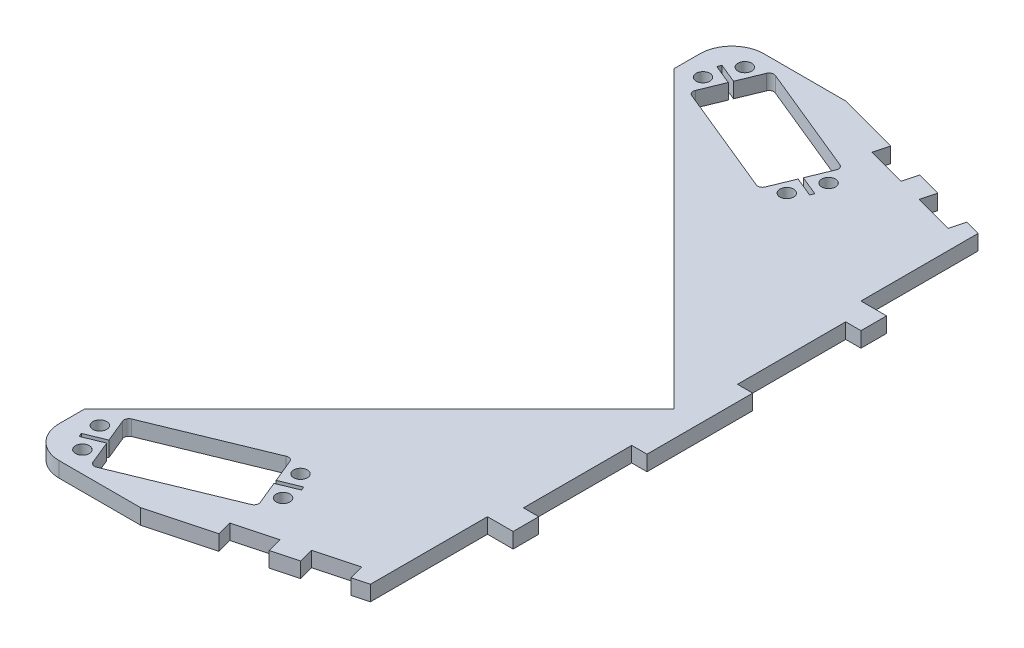
SolidWorks part; units mm, degrees
ref_plane "Front" through (0, 0, 0) normal (0, 0, 1) x (1, 0, 0)
ref_plane "Top" through (0, 0, 0) normal (0, 1, 0) x (1, 0, 0)
ref_plane "Right" through (0, 0, 0) normal (1, 0, 0) x (0, 0, -1)
ref_axis "side-side" through (80.9, 0, 0) along (-1, 0, 0)
ref_axis "up-down" through (0, 50, 0) along (0, -1, 0)
ref_axis "front-back" through (0, 0, -80.9) along (0, 0, 1)
sketch "Sketch1" plane through (0, 0, 0) normal (0, 1, 0) x (1, 0, 0)
  line L0 (-82.7905, 89.3902) -> (-79.7972, 96.6741)
  line L1 (0, 0) -> (-92, 92)
  line L2 (-92, 92) -> (-92, 110)
  line L3 (-79.322, 97.8303) -> (-76.3287, 105.1142)
  line L4 (-79.322, 97.8303) -> (-76.3287, 105.1142)
  line L5 (-92, 110) -> (-56.6019, 110)
  line L6 (8, 58.293) -> (8, -58.293)
  line L7 (0, 0) -> (58.8362, 0) construction
  line L8 (-92, -110) -> (-56.6019, -110)
  line L9 (-92, -110) -> (-92, -92)
  line L10 (0, 0) -> (-92, -92)
  line L11 (-82.7905, 89.3902) -> (-79.7972, 96.6741)
  line L12 (-42.3244, 82.6259) -> (-42.7995, 81.4697)
  line L13 (-42.7995, 81.4697) -> (-36.6949, 78.961)
  line L14 (-36.6949, 78.961) -> (-36.2198, 80.1172)
  line L15 (-36.2198, 80.1172) -> (-42.3244, 82.6259)
  line L16 (-56.6019, 110) -> (0, 94.8336)
  line L17 (-42.7995, 81.4697) -> (-36.6949, 78.961)
  line L18 (-36.6949, 78.961) -> (-36.2198, 80.1172)
  line L19 (-36.2198, 80.1172) -> (-42.3244, 82.6259)
  line L20 (-85.4267, 100.339) -> (-85.9018, 99.1828)
  line L21 (-85.9018, 99.1828) -> (-79.7972, 96.6741)
  line L22 (-79.7972, 96.6741) -> (-79.322, 97.8303)
  line L23 (-79.322, 97.8303) -> (-85.4267, 100.339)
  line L24 (-85.4267, 100.339) -> (-85.9018, 99.1828)
  line L25 (-85.9018, 99.1828) -> (-79.7972, 96.6741)
  line L26 (0, -94.8336) -> (-56.6019, -110)
  line L27 (-79.322, 97.8303) -> (-85.4267, 100.339)
  line L28 (-40.1483, 91.8674) -> (-74.3711, 105.9314)
  line L29 (-40.1483, 91.8674) -> (-74.3711, 105.9314)
  line L30 (-39.331, 89.9098) -> (-42.3244, 82.6259)
  line L31 (-42.7995, 81.4697) -> (-45.7929, 74.1858)
  line L32 (-42.7995, 81.4697) -> (-45.7929, 74.1858)
  line L33 (-39.331, 89.9098) -> (-42.3244, 82.6259)
  line L34 (-47.7504, 73.3685) -> (-81.9733, 87.4326)
  line L35 (-47.7504, 73.3685) -> (-81.9733, 87.4326)
  line L36 (-47.7504, -73.3685) -> (-81.9733, -87.4326)
  line L37 (-39.331, -89.9098) -> (-42.3244, -82.6259)
  line L38 (-42.7995, -81.4697) -> (-45.7929, -74.1858)
  line L39 (-40.1483, -91.8674) -> (-74.3711, -105.9314)
  line L40 (-79.322, -97.8303) -> (-85.4267, -100.339)
  line L41 (-85.9018, -99.1828) -> (-79.7972, -96.6741)
  line L42 (-85.4267, -100.339) -> (-85.9018, -99.1828)
  line L43 (-36.2198, -80.1172) -> (-42.3244, -82.6259)
  line L44 (-36.6949, -78.961) -> (-36.2198, -80.1172)
  line L45 (-42.7995, -81.4697) -> (-36.6949, -78.961)
  line L46 (-82.7905, -89.3902) -> (-79.7972, -96.6741)
  line L47 (-79.322, -97.8303) -> (-76.3287, -105.1142)
  line L50 (0, 94.8336) -> (0, 58.293)
  line L51 (0, 58.293) -> (8, 58.293)
  line L52 (0, -94.8336) -> (0, -58.293)
  line L53 (0, -58.293) -> (8, -58.293)
  arc A0 (-87.2208, 93.5353) -> (-86.1945, 96.0326) centre (-85.1599, 94.1479) ccw construction
  circle A1 centre (-85.1599, 94.1479) radius 2.15
  arc A2 (-83.4197, 102.7847) -> (-82.3934, 105.282) centre (-81.3588, 103.3973) ccw construction
  circle A3 centre (-81.3588, 103.3973) radius 2.15
  arc A4 (-34.9008, 85.7647) -> (-35.9271, 83.2673) centre (-36.9616, 85.1521) ccw construction
  circle A5 centre (-36.9616, 85.1521) radius 2.15
  arc A6 (-38.7018, 76.5153) -> (-39.7281, 74.0179) centre (-40.7627, 75.9026) ccw construction
  circle A7 centre (-40.7627, 75.9026) radius 2.15
  arc A8 (-74.3711, 105.9314) -> (-75.7356, 105.8164) centre (-74.9413, 104.544) ccw
  arc A9 (-75.7356, 105.8164) -> (-76.3287, 105.1142) centre (-74.9413, 104.544) ccw
  arc A10 (-75.7356, 105.8164) -> (-76.3287, 105.1142) centre (-74.9413, 104.544) ccw
  arc A11 (-74.3711, 105.9314) -> (-75.7356, 105.8164) centre (-74.9413, 104.544) ccw
  arc A12 (-82.7905, 89.3902) -> (-82.8626, 88.4738) centre (-81.4031, 88.82) ccw
  arc A13 (-82.8626, 88.4738) -> (-81.9733, 87.4326) centre (-81.4031, 88.82) ccw
  arc A14 (-82.8626, 88.4738) -> (-81.9733, 87.4326) centre (-81.4031, 88.82) ccw
  arc A15 (-82.7905, 89.3902) -> (-82.8626, 88.4738) centre (-81.4031, 88.82) ccw
  arc A16 (-39.331, 89.9098) -> (-39.2589, 90.8262) centre (-40.7184, 90.48) ccw
  arc A17 (-39.2589, 90.8262) -> (-40.1483, 91.8674) centre (-40.7184, 90.48) ccw
  arc A18 (-39.2589, 90.8262) -> (-40.1483, 91.8674) centre (-40.7184, 90.48) ccw
  arc A19 (-39.331, 89.9098) -> (-39.2589, 90.8262) centre (-40.7184, 90.48) ccw
  arc A20 (-46.386, 73.4835) -> (-45.7929, 74.1858) centre (-47.1803, 74.756) ccw
  arc A21 (-47.7504, 73.3685) -> (-46.386, 73.4835) centre (-47.1803, 74.756) ccw
  arc A22 (-47.7504, 73.3685) -> (-46.386, 73.4835) centre (-47.1803, 74.756) ccw
  arc A23 (-46.386, 73.4835) -> (-45.7929, 74.1858) centre (-47.1803, 74.756) ccw
  arc A24 (-46.386, -73.4835) -> (-45.7929, -74.1858) centre (-47.1803, -74.756) cw
  arc A25 (-47.7504, -73.3685) -> (-46.386, -73.4835) centre (-47.1803, -74.756) cw
  arc A26 (-39.331, -89.9098) -> (-39.2589, -90.8262) centre (-40.7184, -90.48) cw
  arc A27 (-39.2589, -90.8262) -> (-40.1483, -91.8674) centre (-40.7184, -90.48) cw
  arc A28 (-82.7905, -89.3902) -> (-82.8626, -88.4738) centre (-81.4031, -88.82) cw
  arc A29 (-82.8626, -88.4738) -> (-81.9733, -87.4326) centre (-81.4031, -88.82) cw
  arc A30 (-74.3711, -105.9314) -> (-75.7356, -105.8164) centre (-74.9413, -104.544) cw
  arc A31 (-75.7356, -105.8164) -> (-76.3287, -105.1142) centre (-74.9413, -104.544) cw
  circle A32 centre (-40.7627, -75.9026) radius 2.15
  circle A33 centre (-36.9616, -85.1521) radius 2.15
  circle A34 centre (-81.3588, -103.3973) radius 2.15
  circle A35 centre (-85.1599, -94.1479) radius 2.15
  dimension "D1" = 45
  dimension "D2" = 110
  dimension "D3" = 8
  dimension "D4" = 100
  dimension "D7" = 75
  dimension "D8" = 13.2562
  dimension "D9" = 64.6019
  dimension "D10" = 8
  dimension "D11" = 116.586
  dimension "D5" = 0
  dimension "D6" = 0
extrude "Boss-Extrude1" add sketch "Sketch1" along normal blind 4.7625
fillet "Fillet1" radius 10 2 edges at (-92, 2.3813, 110) (-92, 2.3813, -110)
sketch "Sketch2" plane through (0, 0, 0) normal (0, 1, 0) x (1, 0, 0)
  line L4 (-4.8296, 96.1276) -> (-17.1928, 99.4404)
  line L5 (-6.0623, 91.5274) -> (-4.8296, 96.1276)
  line L6 (-18.4255, 94.8401) -> (-6.0623, 91.5274)
  line L7 (-17.1928, 99.4404) -> (-18.4255, 94.8401)
  line L8 (-4.8296, 96.1276) -> (-17.1928, 99.4404)
  line L9 (-6.0623, 91.5274) -> (-4.8296, 96.1276)
  line L10 (-18.4255, 94.8401) -> (-6.0623, 91.5274)
  line L11 (-17.1928, 99.4404) -> (-18.4255, 94.8401)
  line L12 (-24.9202, 101.5109) -> (-37.2834, 104.8236)
  line L13 (-26.1529, 96.9107) -> (-24.9202, 101.5109)
  line L14 (-38.5161, 100.2234) -> (-26.1529, 96.9107)
  line L15 (-37.2834, 104.8236) -> (-38.5161, 100.2234)
  line L16 (-24.9202, 101.5109) -> (-37.2834, 104.8236)
  line L17 (-26.1529, 96.9107) -> (-24.9202, 101.5109)
  line L18 (-38.5161, 100.2234) -> (-26.1529, 96.9107)
  line L19 (-37.2834, 104.8236) -> (-38.5161, 100.2234)
  line L20 (-26.1529, -96.9107) -> (-38.5161, -100.2234)
  line L21 (-24.9202, -101.5109) -> (-26.1529, -96.9107)
  line L22 (-37.2834, -104.8236) -> (-24.9202, -101.5109)
  line L23 (-38.5161, -100.2234) -> (-37.2834, -104.8236)
  line L24 (-26.1529, -96.9107) -> (-38.5161, -100.2234)
  line L25 (-24.9202, -101.5109) -> (-26.1529, -96.9107)
  line L26 (-37.2834, -104.8236) -> (-24.9202, -101.5109)
  line L27 (-38.5161, -100.2234) -> (-37.2834, -104.8236)
  line L28 (-6.0623, -91.5274) -> (-18.4255, -94.8401)
  line L29 (-4.8296, -96.1276) -> (-6.0623, -91.5274)
  line L30 (-17.1928, -99.4404) -> (-4.8296, -96.1276)
  line L31 (-18.4255, -94.8401) -> (-17.1928, -99.4404)
  line L32 (-6.0623, -91.5274) -> (-18.4255, -94.8401)
  line L33 (-4.8296, -96.1276) -> (-6.0623, -91.5274)
  line L34 (-17.1928, -99.4404) -> (-4.8296, -96.1276)
  line L35 (-18.4255, -94.8401) -> (-17.1928, -99.4404)
  line L64 (8, 50.293) -> (3.2375, 50.293) construction
  line L65 (3.2375, 50.293) -> (3.2375, 16.51) construction
  line L66 (8, 50.293) -> (8, 16.51) construction
  line L67 (8, 16.51) -> (3.2375, 16.51) construction
  line L68 (8, -16.51) -> (3.2375, -16.51) construction
  line L69 (8, -50.293) -> (8, -16.51) construction
  line L70 (8, -50.293) -> (3.2375, -50.293) construction
  line L71 (3.2375, -50.293) -> (3.2375, -16.51) construction
  line L72 (8, 50.293) -> (3.2375, 50.293)
  line L73 (3.2375, 50.293) -> (3.2375, 16.51)
  line L74 (8, 50.293) -> (8, 16.51)
  line L75 (8, 16.51) -> (3.2375, 16.51)
  line L76 (8, -16.51) -> (3.2375, -16.51)
  line L77 (8, -50.293) -> (8, -16.51)
  line L78 (8, -50.293) -> (3.2375, -50.293)
  line L79 (3.2375, -50.293) -> (3.2375, -16.51)
  dimension "D1" = 0
  dimension "D2" = 0
  dimension "D3" = 0
  dimension "D4" = 0
extrude "Cut-Extrude1" cut sketch "Sketch2" along normal blind 10
